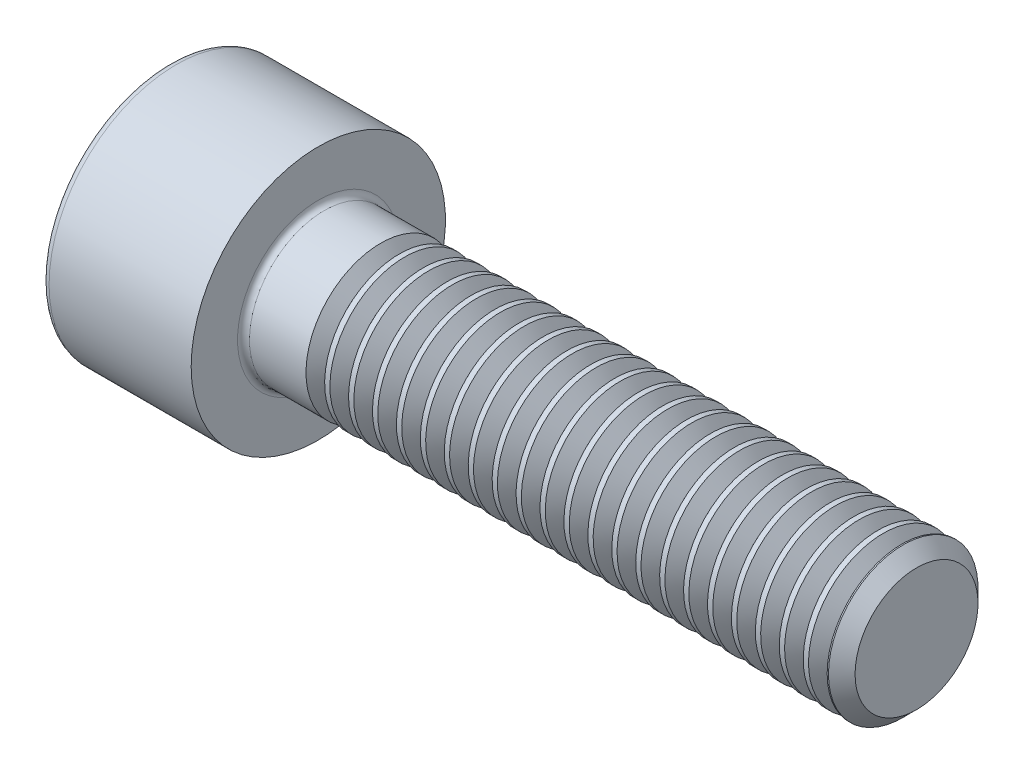
SolidWorks part; units mm, degrees
revolve "Base-Revolve" add sketch "BodySke"
sketch "BodySke" plane through (0, 0, 0) normal (0, 0, 1) x (1, 0, 0)
  line L0 (0, 0) -> (0, 4.25)
  line L1 (0, 4.25) -> (5, 4.25)
  line L2 (5, 4.25) -> (5, 2.5)
  line L3 (5, 2.5) -> (24.555, 2.5)
  line L4 (25, 2.055) -> (25, 0)
  line L5 (25, 0) -> (0, 0)
  line L6 (-31.75, 0) -> (127, 0) construction
  line L8 (25, 2.055) -> (24.555, 2.5)
  line L10 (25, -2.055) -> (24.555, -2.5) construction
  line L11 (5.8, 9.525) -> (5.8, 3.175) construction
  line L12 (5, 9.525) -> (5, 3.175) construction
  line L13 (-35, 9.525) -> (-35, 3.175) construction
  dimension "Diameter" = 5
  dimension "Head_dia" = 8.5
cosmetic thread "ThreadCosmetic" [suppressed]
fillet "Fillet1" radius 0.2 1 edges at (5, 0, 2.5)
fillet "Fillet2" radius 0.25 1 edges at (0, 0, 4.25)
ref_plane "Plane1" through (0, 0, 0) normal (0, 0, 1) x (1, 0, 0)
ref_plane "Plane2" through (0, 0, 0) normal (0, 1, 0) x (1, 0, 0)
ref_plane "Plane3" through (0, 0, 0) normal (1, 0, 0) x (0, 0, -1)
sketch "Sketch2" plane through (0, 0, 0) normal (0, 0, 1) x (1, 0, 0)
  line L0 (0, 2.042) -> (2.5, 2.042)
  line L1 (2.5, 2.042) -> (3.6789, 0)
  line L2 (-31.75, 0) -> (127, 0) construction
  line L3 (3.6789, 0) -> (0, 0)
  line L4 (0, 0) -> (0, 2.042)
  line L6 (0, 0) -> (47.625, 0) construction
  dimension "D1" = 2.042
  dimension "D2" = 60
revolve "Hex-PreBroach" cut sketch "Sketch2" angle 360 about L6
sketch "Sketch3" plane through (0, 0, 0) normal (-1, 0, 0) x (0, 0.5, 0.866)
  line L0 (1.1789, 2.042) -> (-1.1789, 2.042)
  line L1 (-1.1789, 2.042) -> (-2.3579, 0)
  line L2 (1.1789, 2.042) -> (2.3579, 0)
  line L3 (1.1789, -2.042) -> (2.3579, 0)
  line L4 (1.1789, -2.042) -> (-1.1789, -2.042)
  line L5 (-1.1789, -2.042) -> (-2.3579, 0)
  dimension "D1" = 2.042
  dimension "D2" = 2.042
extrude "Hex" cut sketch "Sketch3" against normal blind 2.5
sketch "ThdSchSke" plane through (0, 0, 0) normal (0, 0, 1) x (1, 0, 0)
  line L0 (7.4, -2.055) -> (7.0884, -2.5)
  line L1 (7.4, -2.055) -> (7.7116, -2.5)
  line L2 (7.7116, -2.5) -> (7.7116, -3.125)
  line L3 (-3.175, 0) -> (5.1513, 0) construction
  line L4 (0, 4) -> (0, -4) construction
  line L5 (7.7116, -3.125) -> (7.0884, -3.125)
  line L6 (7.0884, -3.125) -> (7.0884, -2.5)
  dimension "Diameter" = 5
  dimension "Thread_minor" = 4.11
  dimension "Start" = 7.4
revolve "ThreadSchematic" cut sketch "ThdSchSke" angle 360 about L3
pattern_linear "ThdSchPat" count 23 spacing 0.8 along (1, 0, 0) of "ThreadSchematic"
equation "\"D2@Sketch3\" = \"Hex_size@Sketch3\" / 2"
equation "\"D1@Sketch3\" = \"Hex_size@Sketch3\" / 2"
equation "\"D1@Sketch2\" = \"Hex_size@Sketch3\" / 2"
equation "\"Thread_minor@ThreadCosmetic\"  =  \"Minor_dia@BodySke\""
equation "\"Depth@Sketch2\" =  \"Key_eng@Hex\""
equation "\"Thread_length@ThreadCosmetic\" = ((sgn( (\"Length@BodySke\" - \"Advance@BodySke\" * 3.0) - \"Thread_nom@BodySke\" )-1)*( (\"Length@BodySke\" - \"Advance@BodySke\" * 3.0) - \"Thread_nom@BodySke\" ))/-2+ \"Thread_nom@BodySke\""
equation "\"Thread_minor@ThdSchSke\" = \"Minor_dia@BodySke\""
equation "\"Diameter@ThdSchSke\" = \"Diameter@BodySke\""
equation "\"Overcut@ThdSchSke\" = \"Diameter@BodySke\" * 1.25"
equation "\"Start@ThdSchSke\" = \"Head_ht@BodySke\" + \"Length@BodySke\" - \"Thread_length@ThreadCosmetic\"  '---Non-countersunk---"
equation "\"Num_threads@ThdSchPat\" = int( \"Thread_length@ThreadCosmetic\" / \"Advance@BodySke\" + 0.999 )  + 1"
equation "\"Advance@ThdSchPat\" = \"Thread_length@ThreadCosmetic\" /  (\"Num_threads@ThdSchPat\" - 1) 'relax it"
equation "\"Num_threads@ThdSchPat\" = \"Num_threads@ThdSchPat\" - sgn( \"Num_threads@ThdSchPat\" - 1) '---chamfered tips only---"
